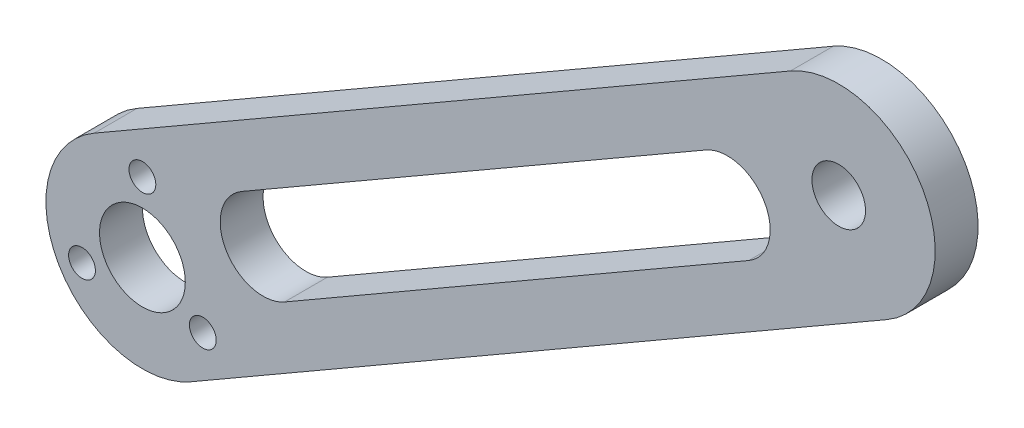
SolidWorks part; units mm, degrees
material "Thornel Mat VMA"
ref_plane "Front Plane" through (0, 0, 0) normal (0, 0, 1) x (1, 0, 0)
ref_plane "Top Plane" through (0, 0, 0) normal (0, 1, 0) x (1, 0, 0)
ref_plane "Right Plane" through (0, 0, 0) normal (1, 0, 0) x (0, 0, -1)
sketch "Sketch1" plane through (0, 0, 0) normal (0, 0, 1) x (1, 0, 0)
  line L0 (0, 0) -> (64.9519, 37.5) construction
  line L1 (0, 0) -> (51.301, 0) construction
  line L2 (60.4519, 45.2942) -> (-4.5, 7.7942)
  line L3 (4.5, -7.7942) -> (69.4519, 29.7058)
  line L4 (5.6338, -3.2527) -> (-5.6338, -3.2527) construction
  line L5 (-5.6338, -3.2527) -> (0, 6.5054) construction
  line L6 (0, 6.5054) -> (5.6338, -3.2527) construction
  circle A5 centre (0, 0) radius 4
  circle A6 centre (0, 6.5054) radius 1.25
  circle A7 centre (5.6338, -3.2527) radius 1.25
  circle A8 centre (-5.6338, -3.2527) radius 1.25
  circle A9 centre (0, 0) radius 9
  circle A10 centre (64.9519, 37.5) radius 2.5
  circle A11 centre (64.9519, 37.5) radius 9
  circle A12 centre (0, 0) radius 6.5054 construction
  dimension "D2" = 5
  dimension "D4" = 18
  dimension "D5" = 18
  dimension "D7" = 8
  dimension "D8" = 2.5
  dimension "D1" = 75
  dimension "D3" = 30
  dimension "D6" = 11.2677
extrude "Boss-Extrude1" add sketch "Sketch1" along normal blind 4 contours A9 A5 A6 A7 A8 | A11 L2 A9 L3 | A11 A10 region at (32.476, 18.75, 0) region at (69.3246, 45.0738, 0) region at (4.3727, 7.5738, 0)
sketch "Sketch2" plane through (0, 0, 4) normal (0, 0, 1) x (1, 0, 0)
  line L0 (11.2583, 6.5) -> (54.5596, 31.5) construction
  line L1 (9.2583, 9.9641) -> (52.5596, 34.9641)
  line L2 (13.2583, 3.0359) -> (56.5596, 28.0359)
  line L3 (60.4519, 45.2942) -> (-4.5, 7.7942) construction
  arc A0 (9.2583, 9.9641) -> (13.2583, 3.0359) centre (11.2583, 6.5) ccw
  arc A1 (56.5596, 28.0359) -> (52.5596, 34.9641) centre (54.5596, 31.5) ccw
  circle A2 centre (64.9519, 37.5) radius 2.5 construction
  point P2 (32.909, 19)
  point P10 (59.4582, 34.3282)
  point P11 (54.9779, 31.7415)
  dimension "D1" = 4
  dimension "D2" = 50
  dimension "D3" = 12
extrude "Cut-Extrude1" cut sketch "Sketch2" against normal blind 10
